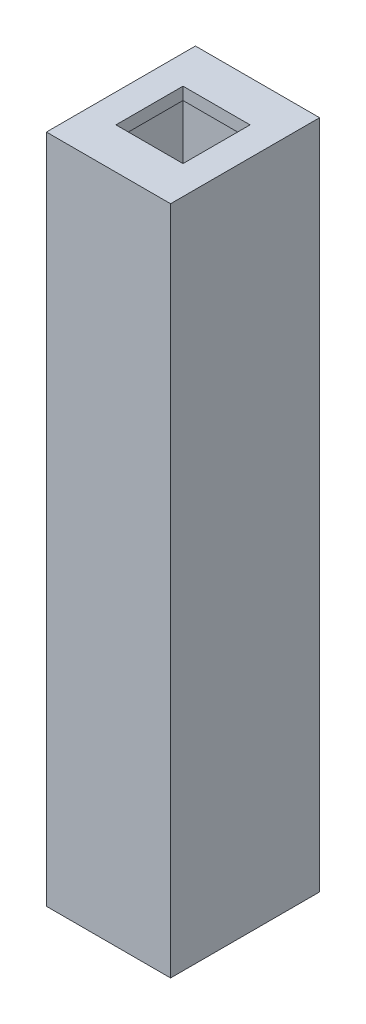
SolidWorks part; units mm, degrees
ref_plane "前视基准面" through (0, 0, 0) normal (0, 0, 1) x (1, 0, 0)
ref_plane "上视基准面" through (0, 0, 0) normal (0, 1, 0) x (1, 0, 0)
ref_plane "右视基准面" through (0, 0, 0) normal (1, 0, 0) x (0, 0, -1)
other "Configuration Table"
sketch "草图1" plane through (0, 0, 0) normal (0, 1, 0) x (1, 0, 0)
  line L1 (-3.1, 3.1) -> (3.1, 3.1)
  line L2 (-3.1, 3.1) -> (-3.1, -3.1)
  line L3 (-3.1, -3.1) -> (3.1, -3.1)
  line L4 (3.1, 3.1) -> (3.1, -3.1)
  line L5 (-3.1, 3.1) -> (3.1, -3.1) construction
  line L6 (-3.1, -3.1) -> (3.1, 3.1) construction
  line L7 (-5, 6) -> (5, 6)
  line L8 (-5, 6) -> (-5, -6)
  line L9 (-5, -6) -> (5, -6)
  line L10 (5, 6) -> (5, -6)
  line L11 (-5, 6) -> (5, -6) construction
  line L12 (-5, -6) -> (5, 6) construction
  line L13 (-2.7, -2.7) -> (2.7, -2.7)
  line L14 (-2.7, -2.7) -> (-2.7, 2.7)
  line L15 (-2.7, 2.7) -> (2.7, 2.7)
  line L16 (2.7, -2.7) -> (2.7, 2.7)
  line L17 (-2.7, -2.7) -> (2.7, 2.7) construction
  line L18 (-2.7, 2.7) -> (2.7, -2.7) construction
  point P0 (0, 0)
  point P5 (0, 0)
  point P13 (0, 0)
  dimension "D1" = 6.2
  dimension "D2" = 12
  dimension "D3" = 5.4
  dimension "D4" = 10
extrude "凸台-拉伸1" add sketch "草图1" along normal blind 54 contours L10 L7 L8 L9 L1 L4 L3 L2 region at (0, 0, -5.8438)
extrude "凸台-拉伸2" add sketch "草图1<3>" against normal blind 1 from surface contours L10 L7 L8 L9 L1 L4 L3 L2 | L4 L1 L2 L3 L16 L13 L14 L15 region at (0, 0, -3.0123) region at (0, 0, -5.8438) starting at face at (0, 54, 0)
sketch "草图1<3>" plane through (0, 0, 0) normal (0, 1, 0) x (1, 0, 0) same geometry as "草图1"
sketch "草图2" plane through (0, 0, 0) normal (0, -1, 0) x (1, 0, 0)
  line L1 (-3, -3) -> (3, -3)
  line L2 (-3, -3) -> (-3, 3)
  line L3 (-3, 3) -> (3, 3)
  line L4 (3, -3) -> (3, 3)
  line L5 (-3, -3) -> (3, 3) construction
  line L6 (-3, 3) -> (3, -3) construction
  circle A0 centre (-3.75, 4.5) radius 0.3
  circle A1 centre (3.75, -4.5) radius 0.3
  circle A2 centre (3.75, 4.5) radius 0.3
  circle A3 centre (-3.75, -4.5) radius 0.3
  point P0 (0, 0)
  dimension "D2" = 0.6
  dimension "D1" = 6
extrude "切除-拉伸1" cut sketch "草图2" against normal blind 2 contours A0 | A2 | A3 | A1
